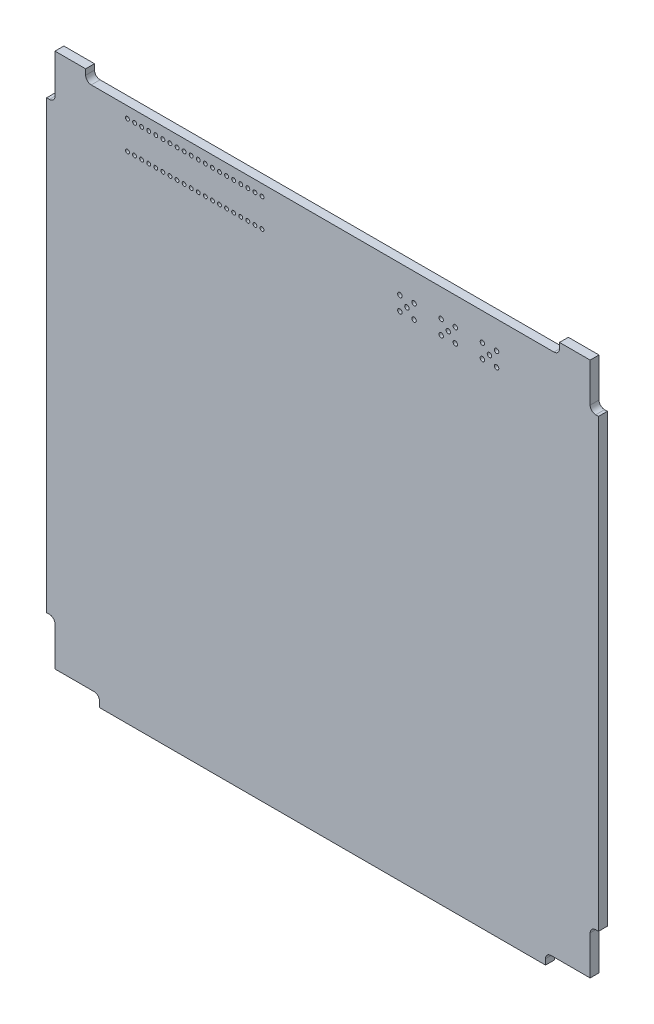
SolidWorks part; units mm, degrees
material "ABS"
ref_plane "Front Plane" through (0, 0, 0) normal (0, 0, 1) x (1, 0, 0)
ref_plane "Top Plane" through (0, 0, 0) normal (0, 1, 0) x (1, 0, 0)
ref_plane "Right Plane" through (0, 0, 0) normal (1, 0, 0) x (0, 0, -1)
sketch "Sketch1" plane through (0, 0, 0) normal (0, 0, 1) x (1, 0, 0)
  line L0 (-40, 50) -> (-40, 48)
  line L1 (-50, -50) -> (50, -50)
  line L2 (-50, -50) -> (-50, 50)
  line L3 (-50, 50) -> (50, 50)
  line L4 (50, -50) -> (50, 50)
  line L5 (-50, -50) -> (50, 50) construction
  line L6 (-50, 50) -> (50, -50) construction
  line L7 (-50, 50) -> (-40, 50)
  line L8 (-50, 50) -> (-50, 40)
  line L9 (-40, 48) -> (-48, 48)
  line L10 (-48, 48) -> (-48, 40)
  line L11 (50, 50) -> (40, 50)
  line L12 (50, 50) -> (50, 40)
  line L13 (-48, 40) -> (-50, 40)
  line L14 (50, 40) -> (48, 40)
  line L15 (-50, -50) -> (-37.8649, -50)
  line L16 (-50, -50) -> (-50, -37.8649)
  line L17 (50, 50) -> (50, 40)
  line L18 (50, 50) -> (40, 50)
  line L19 (50, -50) -> (41.5, -50)
  line L20 (50, -50) -> (50, -41.5)
  line L21 (48, 40) -> (48, 48)
  line L22 (48, 48) -> (40, 48)
  line L23 (40, 48) -> (40, 50)
  line L24 (40, -50) -> (40, -48)
  line L25 (50, -50) -> (40, -50)
  line L26 (50, -50) -> (50, -40)
  line L27 (40, -48) -> (48, -48)
  line L28 (48, -48) -> (48, -40)
  line L29 (48, -40) -> (50, -40)
  line L30 (-50, -40) -> (-48, -40)
  line L31 (-50, -50) -> (-50, -40)
  line L32 (-50, -50) -> (-40, -50)
  line L33 (-48, -40) -> (-48, -48)
  line L34 (-48, -48) -> (-40, -48)
  line L35 (-40, -48) -> (-40, -50)
  point P0 (0, 0)
  point P38 (0, 0)
  dimension "D1" = 100
  dimension "D2" = 100
  dimension "D3" = 2
  dimension "D4" = 10
  dimension "D5" = 4
extrude "Boss-Extrude1" add sketch "Sketch1" along normal blind 1.5875 contours L1 L4 L3 L2 region at (0, 0, 0)
sketch "Sketch2" plane through (0, 0, 1.5875) normal (0, 0, 1) x (1, 0, 0)
  line L0 (0, 50) -> (0, -50) construction
  line L1 (-40, 50) -> (40, 50) construction
  line L2 (-40, -50) -> (40, -50) construction
  line L3 (-50, -40) -> (-50, 40) construction
  line L4 (-40, 50) -> (40, 50) construction
  circle A0 centre (-35, 44) radius 0.35
  circle A1 centre (-33.73, 44) radius 0.35
  circle A2 centre (-32.46, 44) radius 0.35
  circle A3 centre (-31.19, 44) radius 0.35
  circle A4 centre (-29.92, 44) radius 0.35
  circle A5 centre (-28.65, 44) radius 0.35
  circle A6 centre (-27.38, 44) radius 0.35
  circle A7 centre (-26.11, 44) radius 0.35
  circle A8 centre (-24.84, 44) radius 0.35
  circle A9 centre (-23.57, 44) radius 0.35
  circle A10 centre (-22.3, 44) radius 0.35
  circle A11 centre (-21.03, 44) radius 0.35
  circle A12 centre (-19.76, 44) radius 0.35
  circle A13 centre (-18.49, 44) radius 0.35
  circle A14 centre (-17.22, 44) radius 0.35
  circle A15 centre (-15.95, 44) radius 0.35
  circle A16 centre (-14.68, 44) radius 0.35
  circle A17 centre (-13.41, 44) radius 0.35
  circle A18 centre (-12.14, 44) radius 0.35
  circle A19 centre (-10.87, 44) radius 0.35
  circle A20 centre (-33.73, 38.92) radius 0.35
  circle A21 centre (-32.46, 38.92) radius 0.35
  circle A22 centre (-31.19, 38.92) radius 0.35
  circle A23 centre (-29.92, 38.92) radius 0.35
  circle A24 centre (-28.65, 38.92) radius 0.35
  circle A25 centre (-27.38, 38.92) radius 0.35
  circle A26 centre (-26.11, 38.92) radius 0.35
  circle A27 centre (-24.84, 38.92) radius 0.35
  circle A28 centre (-23.57, 38.92) radius 0.35
  circle A29 centre (-22.3, 38.92) radius 0.35
  circle A30 centre (-21.03, 38.92) radius 0.35
  circle A31 centre (-19.76, 38.92) radius 0.35
  circle A32 centre (-18.49, 38.92) radius 0.35
  circle A33 centre (-17.22, 38.92) radius 0.35
  circle A34 centre (-15.95, 38.92) radius 0.35
  circle A35 centre (-14.68, 38.92) radius 0.35
  circle A36 centre (-13.41, 38.92) radius 0.35
  circle A37 centre (-12.14, 38.92) radius 0.35
  circle A38 centre (-10.87, 38.92) radius 0.35
  circle A39 centre (-35, 38.92) radius 0.35
  dimension "D1" = 0.7
  dimension "D4" = 15
  dimension "D5" = 6
  dimension "D2" = 5.08
  dimension "D3" = 1.27
extrude "Cut-Extrude1" cut sketch "Sketch2" against normal through all
sketch "Sketch5" plane through (0, 0, 0) normal (0, 0, -1) x (-1, 0, 0)
  line L0 (40, -50) -> (-40, -50) construction
  line L1 (-49.5, 50) -> (49.5, 50)
  line L2 (-49.5, 50) -> (-49.5, -50)
  line L3 (-49.5, -50) -> (49.5, -50)
  line L4 (49.5, 50) -> (49.5, -50)
  line L5 (40, 50) -> (-40, 50) construction
  line L6 (50, -40) -> (50, 40) construction
  dimension "D1" = 99
  dimension "D2" = 0.5
extrude "Cut-Extrude3" cut sketch "Sketch5" against normal through all flip side to cut
sketch "Sketch6" plane through (0, 0, 1.5875) normal (0, 0, 1) x (1, 0, 0)
  line L1 (28.67, 38.4925) -> (31.21, 38.4925) construction
  line L2 (28.67, 38.4925) -> (28.67, 41.0325) construction
  line L3 (28.67, 41.0325) -> (31.21, 41.0325) construction
  line L4 (31.21, 38.4925) -> (31.21, 41.0325) construction
  line L5 (28.67, 38.4925) -> (31.21, 41.0325) construction
  line L6 (28.67, 41.0325) -> (31.21, 38.4925) construction
  line L8 (21.27, 38.4925) -> (23.81, 38.4925) construction
  line L9 (21.27, 38.4925) -> (21.27, 41.0325) construction
  line L10 (21.27, 41.0325) -> (23.81, 41.0325) construction
  line L11 (23.81, 38.4925) -> (23.81, 41.0325) construction
  line L12 (21.27, 38.4925) -> (23.81, 41.0325) construction
  line L13 (21.27, 41.0325) -> (23.81, 38.4925) construction
  line L14 (13.87, 38.4925) -> (16.41, 38.4925) construction
  line L15 (49.5, 40) -> (49.5, -40) construction
  line L16 (-40, 50) -> (40, 50) construction
  line L17 (13.87, 38.4925) -> (13.87, 41.0325) construction
  line L18 (13.87, 41.0325) -> (16.41, 41.0325) construction
  line L19 (16.41, 38.4925) -> (16.41, 41.0325) construction
  line L20 (13.87, 38.4925) -> (16.41, 41.0325) construction
  line L21 (13.87, 41.0325) -> (16.41, 38.4925) construction
  circle A0 centre (29.94, 39.7625) radius 0.4
  circle A1 centre (28.67, 41.0325) radius 0.4
  circle A2 centre (31.21, 41.0325) radius 0.4
  circle A3 centre (31.21, 38.4925) radius 0.4
  circle A4 centre (28.67, 38.4925) radius 0.4
  circle A5 centre (22.54, 39.7625) radius 0.4
  circle A6 centre (21.27, 41.0325) radius 0.4
  circle A7 centre (23.81, 41.0325) radius 0.4
  circle A8 centre (23.81, 38.4925) radius 0.4
  circle A9 centre (21.27, 38.4925) radius 0.4
  circle A10 centre (15.14, 39.7625) radius 0.4
  circle A11 centre (13.87, 41.0325) radius 0.4
  circle A12 centre (16.41, 41.0325) radius 0.4
  circle A13 centre (16.41, 38.4925) radius 0.4
  circle A14 centre (13.87, 38.4925) radius 0.4
  point P23 (27.2, 39.7784)
  point P32 (19.8, 39.7784)
  dimension "D1" = 2.54
  dimension "D2" = 0.8
  dimension "D3" = 2.54
  dimension "D4" = 19.56
  dimension "D5" = 10.2375
  dimension "D6" = 7.4
  dimension "D7" = 3
sketch "Sketch7" plane through (0, 0, 1.5875) normal (0, 0, 1) x (1, 0, 0)
  line L0 (-40, 50) -> (-36.5, 50)
  line L1 (-40, 50) -> (40, 50) construction
  line L2 (-36.5, 50) -> (-36.5, 48)
  line L3 (-36.5, 48) -> (-41.5, 48)
  line L4 (-40, 48) -> (-48, 48) construction
  line L5 (-41.5, 48) -> (-41.5, 41.5)
  line L6 (-41.5, 41.5) -> (-42, 41.5)
  line L7 (-47, 36.5) -> (-47, -36.5)
  line L8 (-40, 50) -> (-49.5, 50)
  line L9 (-49.5, 50) -> (-49.5, -50)
  line L10 (-49.5, -40) -> (-49.5, 40) construction
  line L11 (49.5, 0) -> (-49.5, 0) construction
  line L12 (-40, -50) -> (-49.5, -50)
  line L13 (-41.5, -41.5) -> (-42, -41.5)
  line L14 (-41.5, -48) -> (-41.5, -41.5)
  line L15 (-36.5, -48) -> (-41.5, -48)
  line L16 (-36.5, -50) -> (-36.5, -48)
  line L17 (-40, -50) -> (-36.5, -50)
  line L18 (0, 0) -> (0, -14.0383) construction
  line L19 (40, -50) -> (36.5, -50)
  line L20 (36.5, -50) -> (36.5, -48)
  line L21 (36.5, -48) -> (41.5, -48)
  line L22 (41.5, -48) -> (41.5, -41.5)
  line L23 (41.5, -41.5) -> (42, -41.5)
  line L24 (40, -50) -> (49.5, -50)
  line L25 (49.5, 50) -> (49.5, -50)
  line L26 (40, 50) -> (49.5, 50)
  line L27 (47, 36.5) -> (47, -36.5)
  line L28 (41.5, 41.5) -> (42, 41.5)
  line L29 (41.5, 48) -> (41.5, 41.5)
  line L30 (36.5, 48) -> (41.5, 48)
  line L31 (36.5, 50) -> (36.5, 48)
  line L32 (40, 50) -> (36.5, 50)
  arc A0 (-42, 41.5) -> (-47, 36.5) centre (-42, 36.5) ccw
  arc A1 (-42, -41.5) -> (-47, -36.5) centre (-42, -36.5) cw
  arc A2 (42, -41.5) -> (47, -36.5) centre (42, -36.5) ccw
  arc A3 (42, 41.5) -> (47, 36.5) centre (42, 36.5) cw
  point P25 (-47, 0)
  point P32 (0, 0)
  point P50 (47, 0)
  dimension "D1" = 5
  dimension "D2" = 13
  dimension "D3" = 8
  dimension "D4" = 8.5
  dimension "D5" = 2.5
  dimension "D6" = 5
sketch "Sketch8" plane through (0, 50, 0) normal (0, 1, 0) x (1, 0, 0)
  line L0 (-40, -1.5875) -> (40, -1.5875) construction
  line L1 (-42.5, 0) -> (42.5, 0)
  line L2 (-42.5, 0) -> (-42.5, -1.5875)
  line L3 (-42.5, -1.5875) -> (42.5, -1.5875)
  line L4 (42.5, 0) -> (42.5, -1.5875)
  line L5 (-42.5, 0) -> (42.5, -1.5875) construction
  line L6 (-42.5, -1.5875) -> (42.5, 0) construction
  line L8 (-40, -1.5875) -> (-40, 0) construction
  point P0 (0, -0.7937)
  dimension "D1" = 85
  dimension "D2" = 1.5875
  dimension "D3" = 2.5
extrude "Cut-Extrude4" cut sketch "Sketch8" against normal blind 4
extrude "Cut-Extrude5" cut sketch "Sketch6" against normal through all
fillet "Fillet1" radius 1 8 edges at (-48, -40, 0.7937) (-40, -48, 0.7937) (40, -48, 0.7937) (48, -40, 0.7937) (48, 40, 0.7937) (-48, 40, 0.7937) (42.5, 46, 0.7937) (-42.5, 46, 0.7937)
sketch "Sketch10" plane through (0, 0, 1.5875) normal (0, 0, 1) x (1, 0, 0)
  line L1 (-41.25, 48) -> (41.25, 48)
  line L2 (-41.25, 48) -> (-41.25, 46.4125)
  line L3 (-41.25, 46.4125) -> (41.25, 46.4125)
  line L4 (41.25, 48) -> (41.25, 46.4125)
  line L5 (-41.25, 48) -> (41.25, 46.4125) construction
  line L6 (-41.25, 46.4125) -> (41.25, 48) construction
  line L7 (-36.5, 48) -> (-41.5, 48) construction
  line L9 (41.5, 48) -> (41.5, 41.5) construction
  point P0 (0, 47.2062)
  dimension "D1" = 82.5
  dimension "D2" = 1.5875
  dimension "D3" = 0.25
sketch "Sketch12" plane through (0, 0, 1.5875) normal (0, 0, 1) x (1, 0, 0)
  line L1 (-35.88, 43.875) -> (-9.98, 43.875)
  line L2 (-35.88, 43.875) -> (-35.88, 39.045)
  line L3 (-35.88, 39.045) -> (-9.98, 39.045)
  line L4 (-9.98, 43.875) -> (-9.98, 39.045)
  line L5 (-35.88, 43.875) -> (-9.98, 39.045) construction
  line L6 (-35.88, 39.045) -> (-9.98, 43.875) construction
  circle A0 centre (-35, 38.92) radius 0.35 construction
  circle A1 centre (-35, 44) radius 0.35 construction
  point P0 (-22.93, 41.46)
  dimension "D4" = 2.54
  dimension "D1" = 25.9
  dimension "D2" = 4.83
  dimension "D3" = 0.88
